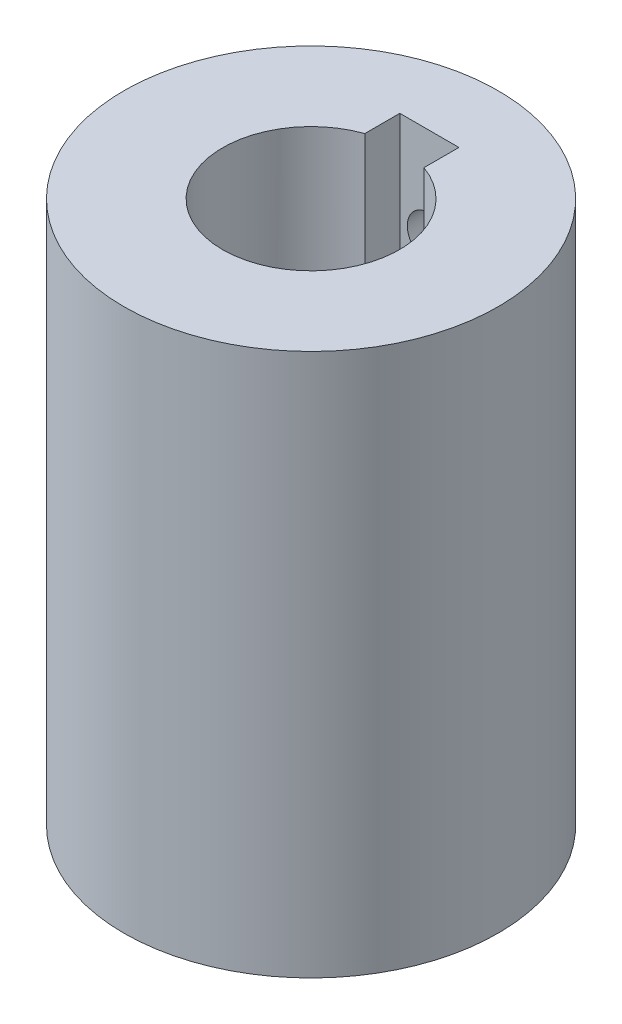
SolidWorks part; units mm, degrees
ref_plane "Front Plane" through (0, 0, 0) normal (0, 0, 1) x (1, 0, 0)
ref_plane "Top Plane" through (0, 0, 0) normal (0, 1, 0) x (1, 0, 0)
ref_plane "Right Plane" through (0, 0, 0) normal (1, 0, 0) x (0, 0, -1)
sketch "Sketch1" plane through (0, 0, 0) normal (0, 1, 0) x (1, 0, 0)
  circle A0 centre (0, 0) radius 12.7
  dimension "D1" = 25.4
extrude "Boss-Extrude1" add sketch "Sketch1" along normal blind 36.83
sketch "Sketch3" plane through (0, 0, 0) normal (0, -1, 0) x (-1, 0, 0)
  circle A0 centre (0, 0) radius 6.35
  dimension "D1" = 12.7
extrude "Cut-Extrude1" cut sketch "Sketch3" against normal blind 18.415
sketch "Sketch4" plane through (0, 36.83, 0) normal (0, 1, 0) x (1, 0, 0)
  circle A0 centre (0, 0) radius 6
  dimension "D1" = 12
extrude "Cut-Extrude2" cut sketch "Sketch4" against normal up to next
sketch "Sketch5" plane through (0, 36.83, 0) normal (0, 1, 0) x (1, 0, 0)
  line L0 (0, 0) -> (0, 8.032) construction
  line L1 (0, 6) -> (3.5883, 6) construction
  line L2 (0, 8.032) -> (-2.0066, 8.032)
  line L3 (-2.0066, 8.032) -> (-2.0066, 5.6545)
  line L4 (0, 8.032) -> (2.0066, 8.032)
  line L5 (2.0066, 8.032) -> (2.0066, 5.6545)
  circle A0 centre (0, 0) radius 6 construction
  arc A1 (2.0066, 5.6545) -> (-2.0066, 5.6545) centre (0, 0) ccw
  point P7 (1.7941, 6)
  dimension "D1" = 2.032
  dimension "D2" = 4.0132
extrude "Cut-Extrude3" cut sketch "Sketch5" against normal up to surface (18.415 mm away) up to face at (0, 18.415, -6)
sketch "Sketch9" plane through (0, 0, 0) normal (0, -1, 0) x (-1, 0, 0)
  line L1 (6.4158, 0) -> (3.2079, 5.5563)
  line L2 (3.2079, 5.5563) -> (-3.2079, 5.5563)
  line L3 (-3.2079, 5.5563) -> (-6.4158, 0)
  line L4 (-6.4158, 0) -> (-3.2079, -5.5563)
  line L5 (-3.2079, -5.5563) -> (3.2079, -5.5563)
  line L6 (3.2079, -5.5563) -> (6.4158, 0)
  circle A0 centre (0, 0) radius 5.5562 construction
  circle A1 centre (0, 0) radius 6.35 construction
  circle A2 centre (0, 0) radius 6.35
  circle M1 centre (0, 0) radius 6.35
  dimension "D1" = 11.1125
extrude "Boss-Extrude2" add sketch "Sketch9" against normal up to surface (18.415 mm away) contours L1 M1 | L6 M1 | L5 M1 | L4 M1 | L3 M1 | L2 M1 region at (-5.0883, 0, -2.9378) region at (-5.0883, 0, 2.9378) region at (0, 0, -5.8755) region at (0, 0, 5.8755) region at (5.0883, 0, -2.9378) region at (5.0883, 0, 2.9378) up to face at (0, 18.415, 0.1677)
extrude "Cut-Extrude6" cut sketch "Sketch9<3>" against normal up to surface (18.415 mm away) contours L4 L5 M1 | L3 L4 M1 | L2 L3 M1 | L1 L2 M1 | L6 L1 M1 | L5 L6 M1 region at (-6.3717, 0, 0) region at (-3.1859, 0, -5.5181) region at (-3.1859, 0, 5.5181) region at (3.1859, 0, -5.5181) region at (3.1859, 0, 5.5181) region at (6.3717, 0, 0) up to face at (6.1608, 18.415, 0)
sketch "Sketch9<3>" plane through (0, 0, 0) normal (0, -1, 0) x (-1, 0, 0) same geometry as "Sketch9"
sketch "Sketch6" plane through (0, 0, 0) normal (0, 0, 1) x (1, 0, 0)
  line L0 (0, 36.83) -> (0, 0) construction
  line L1 (6, 36.83) -> (-6, 36.83) construction
  line L2 (12.7, 36.83) -> (-12.7, 36.83) construction
  line L3 (-12.7, 0) -> (12.7, 0) construction
  circle A0 centre (0, 30.48) radius 1.5
  circle A1 centre (0, 6.35) radius 1.5
  dimension "D1" = 3
  dimension "D2" = 6.35
  dimension "D3" = 6.35
extrude "Cut-Extrude4" cut sketch "Sketch6" against normal up to next
sketch "Sketch7" plane through (0, 0, 0) normal (1, 0, 0) x (0, 0, -1)
  line L0 (0, 36.83) -> (0, 0) construction
  line L1 (12.7, 36.83) -> (-12.7, 36.83) construction
  line L2 (-12.7, 0) -> (12.7, 0) construction
  circle A0 centre (0, 30.48) radius 1.5
  circle A1 centre (0, 6.35) radius 1.5
  dimension "D1" = 3
  dimension "D2" = 6.35
  dimension "D3" = 6.35
